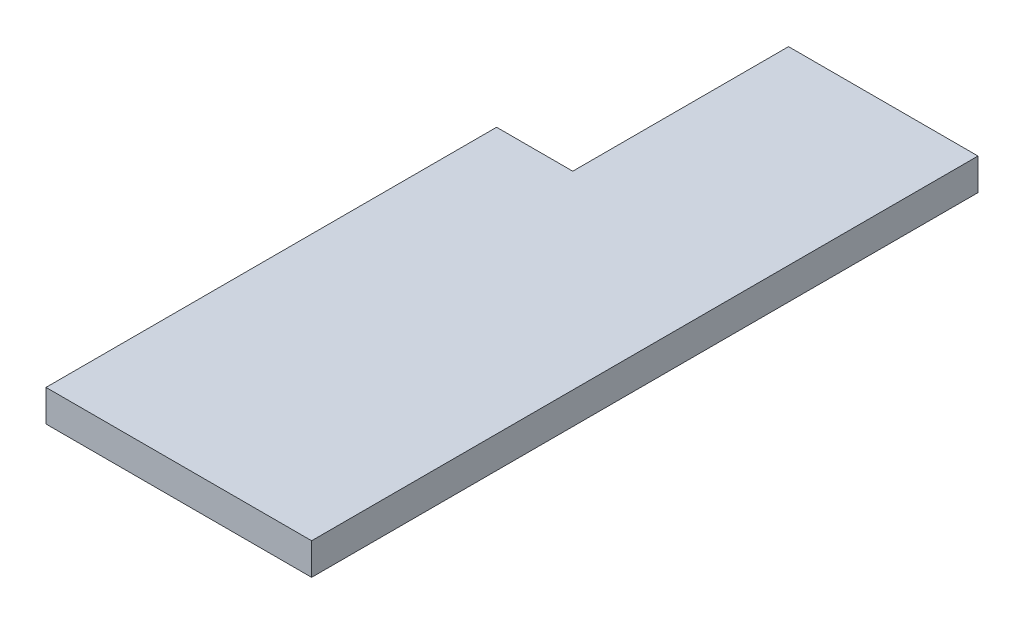
SolidWorks part; units mm, degrees
ref_plane "Front Plane" through (0, 0, 0) normal (0, 0, 1) x (1, 0, 0)
ref_plane "Top Plane" through (0, 0, 0) normal (0, 1, 0) x (1, 0, 0)
ref_plane "Right Plane" through (0, 0, 0) normal (1, 0, 0) x (0, 0, -1)
sketch "Sketch1" plane through (0, 0, 0) normal (0, 1, 0) x (1, 0, 0)
  line L1 (0, 0) -> (-53.594, 0)
  line L2 (0, 0) -> (0, 82.55)
  line L3 (0, 82.55) -> (-53.594, 82.55)
  line L4 (-53.594, 0) -> (-53.594, 82.55)
  dimension "D1" = 82.55
  dimension "D2" = 53.594
extrude "Boss-Extrude1" add sketch "Sketch1" along normal blind 6.35
sketch "Sketch6" plane through (0, 0, 0) normal (0, 0, 1) x (1, 0, 0)
  line L1 (0, 6.35) -> (-53.594, 6.35)
  line L2 (0, 6.35) -> (0, 0)
  line L3 (0, 0) -> (-53.594, 0)
  line L4 (-53.594, 6.35) -> (-53.594, 0)
extrude "Boss-Extrude3" add sketch "Sketch6" along normal blind 7.62
ref_plane "KORAL!!!" through (-26.797, 0, 0) normal (1, 0, 0) x (0, 0, -1)
sketch "Sketch3" plane through (0, 6.35, 0) normal (0, 1, 0) x (1, 0, 0)
  line L1 (0, 82.55) -> (0, -7.62)
  line L2 (-0.508, -7.62) -> (-0.508, 82.55)
  line L3 (0, 82.55) -> (-53.594, 82.55) construction
  line L4 (-0.508, 82.55) -> (0, 82.55)
  line L6 (0, -7.62) -> (-53.594, -7.62) construction
  line L7 (0, -7.62) -> (-0.508, -7.62)
  dimension "D1" = 0.508
extrude "Cut-Extrude2" cut sketch "Sketch3" against normal up to next
mirror "Mirror1" about plane through (-26.797, 0, 0) normal (1, 0, 0) of "Cut-Extrude2"
sketch "Sketch8" plane through (0, 0, -82.55) normal (0, 0, -1) x (-1, 0, 0)
  line L0 (0.508, 0) -> (53.086, 0) construction
  line L1 (0.508, 6.35) -> (37.846, 6.35)
  line L2 (0.508, 6.35) -> (0.508, 0)
  line L3 (0.508, 0) -> (37.846, 0)
  line L4 (37.846, 6.35) -> (37.846, 0)
  line L5 (53.086, 0) -> (53.086, 6.35) construction
  dimension "D1" = 15.24
extrude "Boss-Extrude4" add sketch "Sketch8" along normal blind 43.18
sketch "Sketch9" plane through (0, 0, 0) normal (0, 0, 1) x (1, 0, 0)
  line L0 (7.4165, 3.5859) -> (-19.1601, 49.6179) construction
  line L1 (-19.1601, 49.6179) -> (-33.0389, 49.6179) construction
  line L2 (-33.0389, 49.6179) -> (-59.3747, 3.4478) construction
  line L3 (-59.3747, 3.4478) -> (-53.086, 0) construction
  line L5 (1.2055, 0) -> (7.4165, 3.5859) construction
  line L7 (-53.086, 0) -> (1.2055, 0) construction
  line L10 (-53.086, 6.35) -> (0.0672, 6.35)
  line L11 (-53.086, 6.35) -> (-53.086, 0)
  line L12 (-53.086, 0) -> (0.0672, 0)
  line L13 (0.0672, 6.35) -> (0.0672, 0)
  dimension "D1" = 53.1532
  dimension "D2" = 13.8788
  dimension "D3" = 1.2055
  dimension "D4" = 7.4165
  dimension "D5" = 19.1601
sketch "Sketch10" plane through (0, 0, 7.62) normal (0, 0, 1) x (1, 0, 0)
  line L0 (-33.0389, 49.6179) -> (-59.3747, 3.4478) construction
  line L5 (-53.086, 0) -> (0.0672, 0)
  line L6 (-53.086, 0) -> (-53.086, 6.35)
  line L7 (-53.086, 6.35) -> (0.0672, 6.35)
  line L8 (0.0672, 0) -> (0.0672, 6.35)
  line L9 (-53.086, 6.35) -> (0.0672, 6.35) construction
extrude "Boss-Extrude5" add sketch "Sketch10" against normal up to surface (90.17 mm away) up to face at (-45.466, 3.175, -82.55)
sketch "Sketch11" plane through (0, 0, -82.55) normal (0, 0, -1) x (-1, 0, 0)
  line L1 (-0.0672, 6.35) -> (0.508, 6.35)
  line L2 (-0.0672, 6.35) -> (-0.0672, 0)
  line L3 (-0.0672, 0) -> (0.508, 0)
  line L4 (0.508, 6.35) -> (0.508, 0)
extrude "Boss-Extrude6" add sketch "Sketch11" along normal up to surface (43.18 mm away) up to face at (-19.177, 3.175, -125.73)
